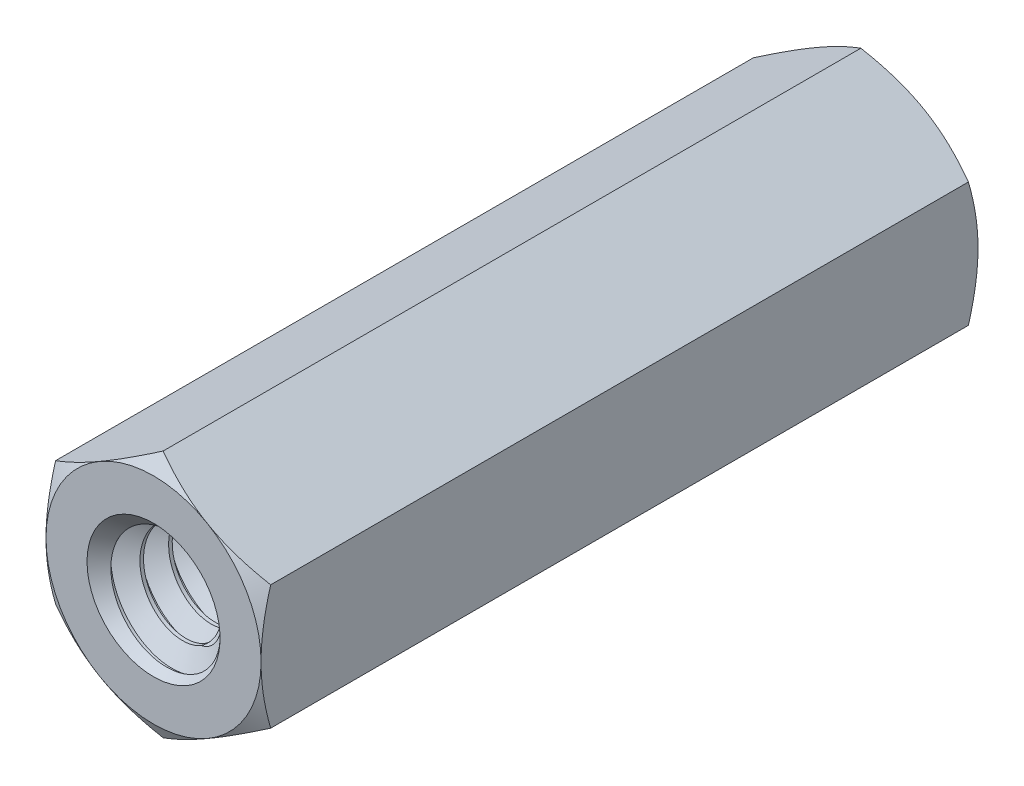
SolidWorks part; units mm, degrees
ref_plane "Front Plane" through (0, 0, 0) normal (0, 0, 1) x (1, 0, 0)
ref_plane "Top Plane" through (0, 0, 0) normal (0, 1, 0) x (1, 0, 0)
ref_plane "Right Plane" through (0, 0, 0) normal (1, 0, 0) x (0, 0, -1)
sketch "Sketch3" plane through (0, 0, 0) normal (1, 0, 0) x (0, 0, -1)
  line L0 (-7.9375, 0) -> (7.9375, 0) construction
  line L1 (0, 2.3813) -> (0, -2.3813) construction
  line L2 (-7.9375, 1.4224) -> (-7.9375, -1.4224) construction
  point P2 (-7.9375, 0)
  point P3 (7.9375, 0)
  dimension "D1" = 15.875
  dimension "Length" = 15.875
  dimension "Min Thread Length" = 15.875
  dimension "Thread Dia" = 2.8448
  dimension "Hex" = 4.7625
sketch "Sketch1" plane through (0, 0, 0) normal (0, 0, 1) x (1, 0, 0)
  line L1 (0, 2.7496) -> (-2.3813, 1.3748)
  line L2 (-2.3813, 1.3748) -> (-2.3813, -1.3748)
  line L3 (-2.3813, -1.3748) -> (0, -2.7496)
  line L4 (0, -2.7496) -> (2.3812, -1.3748)
  line L5 (2.3812, -1.3748) -> (2.3812, 1.3748)
  line L6 (2.3812, 1.3748) -> (0, 2.7496)
  circle A0 centre (0, 0) radius 2.3813 construction
  circle A1 centre (0, 0) radius 1.4224
extrude "Extrude1" add sketch "Sketch1" along normal up to vertex (7.9375 mm away) and the other way up to vertex (7.9375 mm away) up to point (0, 0, 7.9375) other way up to point (0, 0, -7.9375)
sketch "Sketch11" plane through (0, 0, -7.9375) normal (0, 0, -1) x (-1, 0, 0)
  circle A0 centre (0, 0) radius 1.4224 construction
  circle A1 centre (0, 0) radius 1.4224
curve "Helix/Spiral1" pitch 0.635 height 16.51 radius 1.4224 centre (0, 0, -7.9375) axis (0, 0, 1) start towards (0, 1, 0) parameters "Pitch"=0.635
sketch "Sketch12" plane through (0, 0, 0) normal (1, 0, 0) x (0, 0, -1)
  line L0 (8.4931, 1.4224) -> (7.9375, 1.4224)
  line L1 (8.4931, 1.4224) -> (8.255, 1.01)
  line L2 (8.255, 1.01) -> (8.1756, 1.01)
  line L3 (8.1756, 1.01) -> (7.9375, 1.4224)
  line L4 (8.2153, 1.01) -> (8.2153, 1.4224) construction
  line L5 (8.3741, 1.2162) -> (8.0566, 1.2162) construction
  dimension "D1" = 0.0794
  dimension "D2" = 0.3175
  dimension "D3" = 60
sweep "Sweep1" add profiles "Sketch12" path "Helix/Spiral1"
sketch "Sketch6" plane through (0, 0, -7.9375) normal (0, 0, -1) x (-1, 0, 0)
  line L6 (0, 2.7496) -> (-2.3812, 1.3748)
  line L7 (-2.3812, 1.3748) -> (-2.3812, -1.3748)
  line L8 (-2.3812, -1.3748) -> (0, -2.7496)
  line L9 (0, -2.7496) -> (2.3813, -1.3748)
  line L10 (2.3813, -1.3748) -> (2.3813, 1.3748)
  line L11 (2.3813, 1.3748) -> (0, 2.7496)
  line L12 (0, 2.7496) -> (-2.3812, 1.3748)
  line L13 (-2.3812, 1.3748) -> (-2.3812, -1.3748)
  line L14 (-2.3812, -1.3748) -> (0, -2.7496)
  line L15 (0, -2.7496) -> (2.3813, -1.3748)
  line L16 (2.3813, -1.3748) -> (2.3813, 1.3748)
  line L17 (2.3813, 1.3748) -> (0, 2.7496)
  dimension "D1" = 0
extrude "Extrude2" cut sketch "Sketch6" along normal through all
sketch "Sketch7" plane through (0, 0, -7.9375) normal (0, 0, -1) x (-1, 0, 0)
  circle A2 centre (0, 0) radius 1.4732
  circle A3 centre (0, 0) radius 1.4732
  dimension "D1" = 0.0508
extrude "Extrude3" cut sketch "Sketch7" against normal through all draft 43
sketch "Sketch8" plane through (0, 0, -7.9375) normal (0, 0, -1) x (-1, 0, 0)
  circle A0 centre (0, 0) radius 2.3813 construction
  circle A1 centre (0, 0) radius 2.3813
extrude "Extrude4" cut sketch "Sketch8" against normal through all draft 60 flip side to cut
mirror "Mirror1" about plane through (0, 0, 0) normal (0, 0, 1) of "Extrude2", "Extrude3", "Extrude4"
sketch "Sketch9" [suppressed] plane through (0, 0, 0) normal (1, 0, 0) x (0, 0, -1)
  line L1 (-22.225, 3.2258) -> (22.225, 3.2258)
  line L2 (-22.225, 3.2258) -> (-22.225, 0)
  line L3 (-22.225, 0) -> (22.225, 0)
  line L4 (22.225, 3.2258) -> (22.225, 0)
  line L7 (-38.1, 0) -> (38.1, 0) construction
revolve "Revolve" [suppressed] add sketch "Sketch9" angle 360 about L0
sketch "Sketch10" [suppressed] plane through (0, 0, 0) normal (1, 0, 0) x (0, 0, -1)
  line L0 (38.1, 3.175) -> (22.225, 3.175)
  line L1 (-38.1, 3.175) -> (-22.225, 3.175)
  line L2 (22.225, 3.175) -> (22.225, -3.175)
  line L3 (-38.1, -3.2258) -> (-22.225, -3.2258)
  line L4 (-22.225, 3.175) -> (-22.225, -3.2258)
  line L5 (22.225, -3.175) -> (38.1, -3.175)
equation "\"D1@Sketch3\" = \"Min Thread Length@Sketch3\""
equation "\"D3@Helix/Spiral1\" = \"Length@Sketch3\"+\"Pitch@Helix/Spiral1\""
equation "\"D1@Sketch12\" = \"Pitch@Helix/Spiral1\"*.125"
equation "\"D2@Sketch12\" = \"Pitch@Helix/Spiral1\"*.5"
